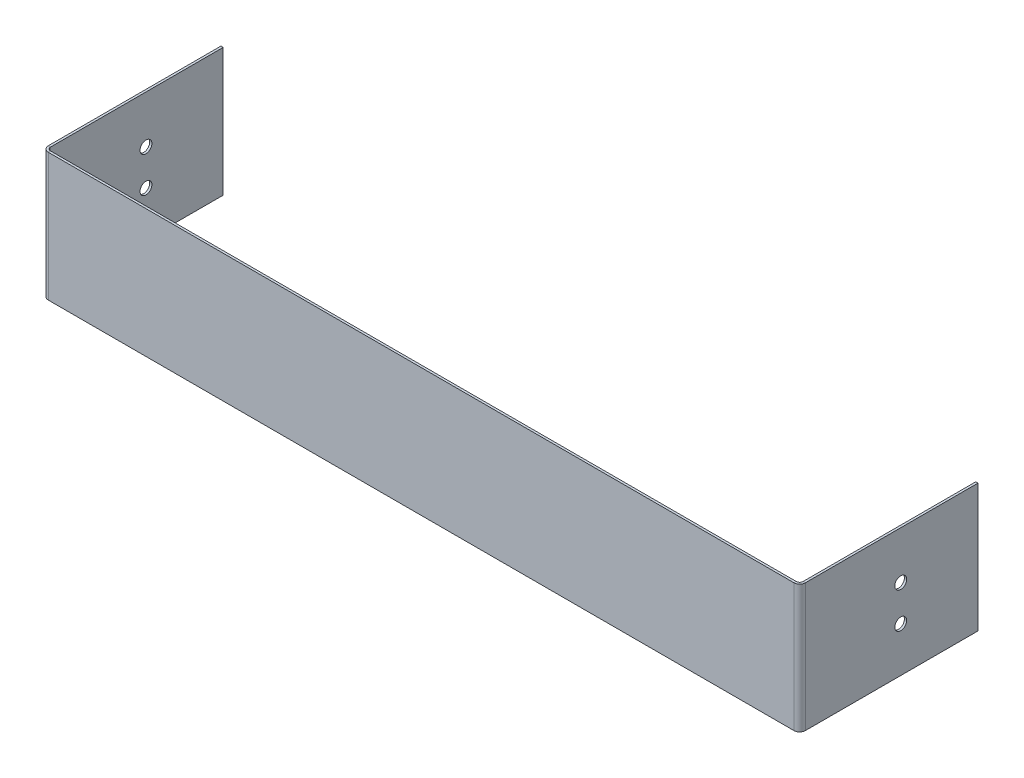
SolidWorks part; units mm, degrees
note: The reader was unsure of these and kept them because the rebuilt part matched: flange length of "Edge-Flange1", "Edge-Flange2".
ref_plane "Front Plane" through (0, 0, 0) normal (0, 0, 1) x (1, 0, 0)
ref_plane "Top Plane" through (0, 0, 0) normal (0, 1, 0) x (1, 0, 0)
ref_plane "Right Plane" through (0, 0, 0) normal (1, 0, 0) x (0, 0, -1)
sketch "Sketch1" plane through (0, 0, 0) normal (0, 0, 1) x (1, 0, 0)
  line L0 (0, 0) -> (161.73, 0)
  line L1 (161.73, 0) -> (161.73, 27.3546)
  line L2 (161.73, 27.3546) -> (0, 27.3546)
  line L3 (0, 27.3546) -> (0, 0)
base flange "Base-Flange1" sketch "Sketch1" thickness 0.4826 reverse thickness direction no parameters "D1"=0.7366
edge flange "Edge-Flange1" sketch "Sketch8" flange angle 90 flange length 38.1 flange position material inside bend radius 0.7366 thickness 0.4826 relief rectangular parameters "D6"=10
sketch "Sketch8" plane through (161.73, 0, -0.4826) normal (1, 0, 0) x (0, -1, 0)
  line L0 (0, 0) -> (-27.3546, 0) construction
  line L1 (0, 0) -> (-27.3546, 0)
  line L2 (-27.3546, 0) -> (-27.3546, 37.6174)
  line L3 (-27.3546, 37.6174) -> (0, 37.6174)
  line L4 (0, 37.6174) -> (0, 0)
bend "EdgeBend1" bend radius 0.7366 bend angle 90 parameters "D5"=1
edge flange "Edge-Flange2" sketch "Sketch11" flange angle 90 flange length 38.1 flange position material inside bend radius 0.7366 thickness 0.4826 relief rectangular parameters "D6"=10
sketch "Sketch11" plane through (0, 0, -0.4826) normal (-1, 0, 0) x (0, 1, 0)
  line L2 (0, 0) -> (0, 37.6174)
  line L3 (0, 37.6174) -> (27.3546, 37.6174)
  line L4 (27.3546, 37.6174) -> (27.3546, 0)
  line L7 (27.3546, 0) -> (0, 0) construction
  line L8 (27.3546, 0) -> (0, 0)
bend "EdgeBend2" bend radius 0.7366 bend angle 90 parameters "D5"=2
sketch "Sketch12" plane through (161.73, 0, 0) normal (1, 0, 0) x (0, 0, -1)
  line L0 (38.1, 27.3546) -> (1.2192, 27.3546) construction
  line L1 (38.1, 0) -> (38.1, 27.3546) construction
  circle A0 centre (21.59, 17.1946) radius 1.27
  circle A1 centre (21.59, 9.5746) radius 1.27
  dimension "D1" = 2.54
  dimension "D2" = 2.54
  dimension "D3" = 7.62
  dimension "D4" = 10.16
  dimension "D5" = 16.51
extrude "Cut-Extrude1" cut sketch "Sketch12" against normal through all normal cut yes
sketch "Bend-Lines1" [suppressed] plane through (0, 0, 0) normal (0, 1, 0) x (1, 0, 0)
sketch "Bounding-Box1" [suppressed] plane through (0, 0, 0) normal (0, 1, 0) x (1, 0, 0)
sheet metal parameters "Sheet-Metal2" thickness 0.4826 parameters "D1"=0.7366
flat pattern "Flat-Pattern2" [suppressed]
sketch "Bend-Lines2" plane through (0, 0, 0) normal (0, 1, 0) x (1, 0, 0)
sketch3d "Bounding-Box2" [suppressed]
  line L0 (0, 0, 0) -> (-161.73, 0, 0) construction
  line L1 (0, 27.3546, 0) -> (-161.73, 27.3546, 0) construction
  line L2 (0, 0, 0) -> (0, 27.3546, 0) construction
  line L3 (-161.73, 0, 0) -> (-161.73, 27.3546, 0) construction
sheet metal parameters "Sheet-Metal3" thickness 0.4826 parameters "D1"=0.7366
flat pattern "Flat-Pattern2"
sketch "Bend-Lines2" plane through (0, 0, 0) normal (0, 0, 1) x (1, 0, 0)
  line L0 (161.2788, 0) -> (161.2788, 27.3546) construction
  line L1 (161.2788, 0) -> (161.2788, 27.3546) construction
sketch3d "Bounding-Box2" [suppressed]
  line L0 (0, 0, 0) -> (194.5335, 0, 0) construction
  line L1 (0, 27.3546, 0) -> (194.5335, 27.3546, 0) construction
  line L2 (0, 0, 0) -> (0, 27.3546, 0) construction
  line L3 (194.5335, 0, 0) -> (194.5335, 27.3546, 0) construction
bend of the flat pattern "Flatten-<EdgeBend1>1"
sheet metal parameters "Sheet-Metal4" thickness 0.4826 parameters "D1"=0.7366
flat pattern "Flat-Pattern2" [suppressed]
sketch "Bend-Lines2" plane through (0, 0, 0) normal (0, 0, 1) x (1, 0, 0)
  line L0 (161.2788, 0) -> (161.2788, 27.3546) construction
  line L1 (161.2788, 0) -> (161.2788, 27.3546) construction
  line L2 (0.4512, 27.3546) -> (0.4512, 0) construction
  line L3 (0.4512, 27.3546) -> (0.4512, 0) construction
sketch3d "Bounding-Box2" [suppressed]
  line L0 (-37.1977, 0, 0) -> (198.9277, 0, 0) construction
  line L1 (-37.1977, 27.3546, 0) -> (198.9277, 27.3546, 0) construction
  line L2 (-37.1977, 0, 0) -> (-37.1977, 27.3546, 0) construction
  line L3 (198.9277, 0, 0) -> (198.9277, 27.3546, 0) construction
bend of the flat pattern "Flatten-<EdgeBend1>1"
bend of the flat pattern "Flatten-<EdgeBend2>1"
sketch "Sketch12-1" [suppressed] plane through (160.8277, 0, 0) normal (0, 0, 1) x (1, 0, 0)
  line L0 (38.1, 27.3546) -> (-198.0253, 27.3546) construction
  line L1 (38.1, 0) -> (38.1, 27.3546) construction
  circle A0 centre (21.59, 17.1946) radius 1.27
  circle A1 centre (21.59, 9.5746) radius 1.27
  dimension "D1" = 2.54
  dimension "D2" = 2.54
  dimension "D3" = 7.62
  dimension "D4" = 10.16
  dimension "D5" = 16.51
sheet metal parameters "Sheet-Metal7" thickness 0.4826 parameters "D1"=0.7366
flat pattern "Flat-Pattern2" [suppressed]
sketch "Bend-Lines2" plane through (0, 0, 0) normal (0, 0, 1) x (1, 0, 0)
  line L0 (161.2788, 0) -> (161.2788, 27.3546) construction
  line L1 (161.2788, 0) -> (161.2788, 27.3546) construction
  line L2 (0.4512, 27.3546) -> (0.4512, 0) construction
  line L3 (0.4512, 27.3546) -> (0.4512, 0) construction
sketch3d "Bounding-Box2" [suppressed]
  line L0 (-37.1977, 0, 0) -> (198.9277, 0, 0) construction
  line L1 (-37.1977, 27.3546, 0) -> (198.9277, 27.3546, 0) construction
  line L2 (-37.1977, 0, 0) -> (-37.1977, 27.3546, 0) construction
  line L3 (198.9277, 0, 0) -> (198.9277, 27.3546, 0) construction
bend of the flat pattern "Flatten-<EdgeBend1>1"
bend of the flat pattern "Flatten-<EdgeBend2>1"
sketch "Sketch12-1" [suppressed] plane through (160.8277, 0, 0) normal (0, 0, 1) x (1, 0, 0)
  line L0 (38.1, 27.3546) -> (-198.0253, 27.3546) construction
  line L1 (38.1, 0) -> (38.1, 27.3546) construction
  circle A0 centre (21.59, 17.1946) radius 1.27
  circle A1 centre (21.59, 9.5746) radius 1.27
  dimension "D1" = 2.54
  dimension "D2" = 2.54
  dimension "D3" = 7.62
  dimension "D4" = 10.16
  dimension "D5" = 16.51
